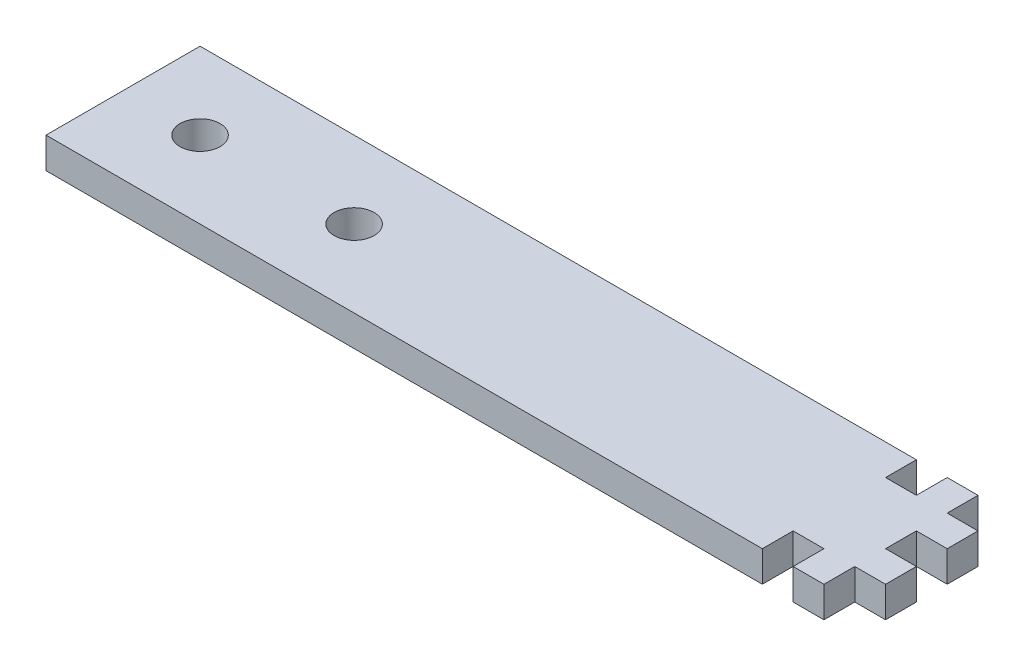
SolidWorks part; units mm, degrees
ref_plane "Front Plane" through (0, 0, 0) normal (0, 0, 1) x (1, 0, 0)
ref_plane "Top Plane" through (0, 0, 0) normal (0, 1, 0) x (1, 0, 0)
ref_plane "Right Plane" through (0, 0, 0) normal (1, 0, 0) x (0, 0, -1)
sketch "Sketch1" plane through (0, 0, 0) normal (0, 1, 0) x (1, 0, 0)
  line L1 (0, 0) -> (66.675, 0)
  line L2 (0, 0) -> (0, 12.7)
  line L3 (0, 12.7) -> (66.675, 12.7)
  line L4 (66.675, 0) -> (66.675, 12.7)
  dimension "D1" = 12.7
  dimension "D2" = 66.675
extrude "Boss-Extrude1" add sketch "Sketch1" along normal blind 2.54
sketch "Sketch3" plane through (0, 2.54, 0) normal (0, 1, 0) x (1, 0, 0)
  line L0 (0, 6.35) -> (66.675, 6.35) construction
  line L1 (0, 12.7) -> (0, 0) construction
  line L2 (66.675, 0) -> (66.675, 12.7) construction
  line L3 (64.135, 12.7) -> (64.135, 10.16)
  line L4 (66.675, 12.7) -> (0, 12.7) construction
  line L5 (64.135, 10.16) -> (66.675, 10.16)
  line L6 (66.675, 10.16) -> (66.675, 7.62)
  line L7 (66.675, 7.62) -> (64.135, 7.62)
  line L8 (64.135, 7.62) -> (64.135, 5.08)
  line L9 (64.135, 5.08) -> (66.675, 5.08)
  line L10 (64.135, 0) -> (64.135, 2.54)
  line L11 (0, 0) -> (66.675, 0) construction
  line L12 (64.135, 2.54) -> (66.675, 2.54)
  line L13 (64.135, 12.7) -> (66.675, 12.7)
  line L14 (66.675, 12.7) -> (66.675, 0)
  line L16 (66.675, 0) -> (64.135, 0)
  line M2 (0, 0) -> (66.675, 0)
  line M3 (66.675, 0) -> (66.675, 12.7)
  line M4 (66.675, 12.7) -> (0, 12.7)
  dimension "D1" = 2.54
  dimension "D2" = 2.54
  dimension "D3" = 2.54
  dimension "D4" = 2.54
extrude "Cut-Extrude1" cut sketch "Sketch3" against normal through all and the other way blind 1.27 contours L3 L5 M3 M4 | L8 L0 L14 L7 | L0 L8 L9 M3 | L12 L10 M2 M3 region at (65.405, 2.54, -6.985) region at (65.405, 2.54, -11.43) region at (65.405, 2.54, -1.27) region at (65.405, 2.54, -5.715)
sketch "Sketch4" plane through (0, 2.54, 0) normal (0, 1, 0) x (1, 0, 0)
  line L0 (0, 6.35) -> (64.135, 6.35) construction
  line L1 (0, 12.7) -> (0, 0) construction
  line L2 (64.135, 7.62) -> (64.135, 5.08) construction
  line L3 (25.4, 12.7) -> (25.4, 0) construction
  line L4 (64.135, 12.7) -> (0, 12.7) construction
  line L5 (0, 0) -> (64.135, 0) construction
  circle A0 centre (6.35, 6.35) radius 1.651
  circle A1 centre (19.05, 6.35) radius 1.651
  dimension "D2" = 12.7
  dimension "D4" = 3.302
  dimension "D1" = 25.4
  dimension "D3" = 6.35
extrude "Cut-Extrude2" cut sketch "Sketch4" against normal through all
sketch "Sketch5" plane through (0, 2.54, 0) normal (0, 1, 0) x (1, 0, 0)
  line L0 (0, 0) -> (64.135, 0) construction
  line L1 (61.595, 0) -> (59.055, 0)
  line L2 (61.595, 0) -> (61.595, 2.54)
  line L3 (61.595, 2.54) -> (59.055, 2.54)
  line L4 (59.055, 0) -> (59.055, 2.54)
  line L5 (64.135, 12.7) -> (0, 12.7) construction
  line L6 (59.055, 12.7) -> (61.595, 12.7)
  line L7 (59.055, 12.7) -> (59.055, 10.16)
  line L8 (59.055, 10.16) -> (61.595, 10.16)
  line L9 (61.595, 12.7) -> (61.595, 10.16)
  line L10 (64.135, 2.54) -> (64.135, 0) construction
  dimension "D1" = 2.54
  dimension "D2" = 2.54
extrude "Cut-Extrude3" cut sketch "Sketch5" against normal through all
